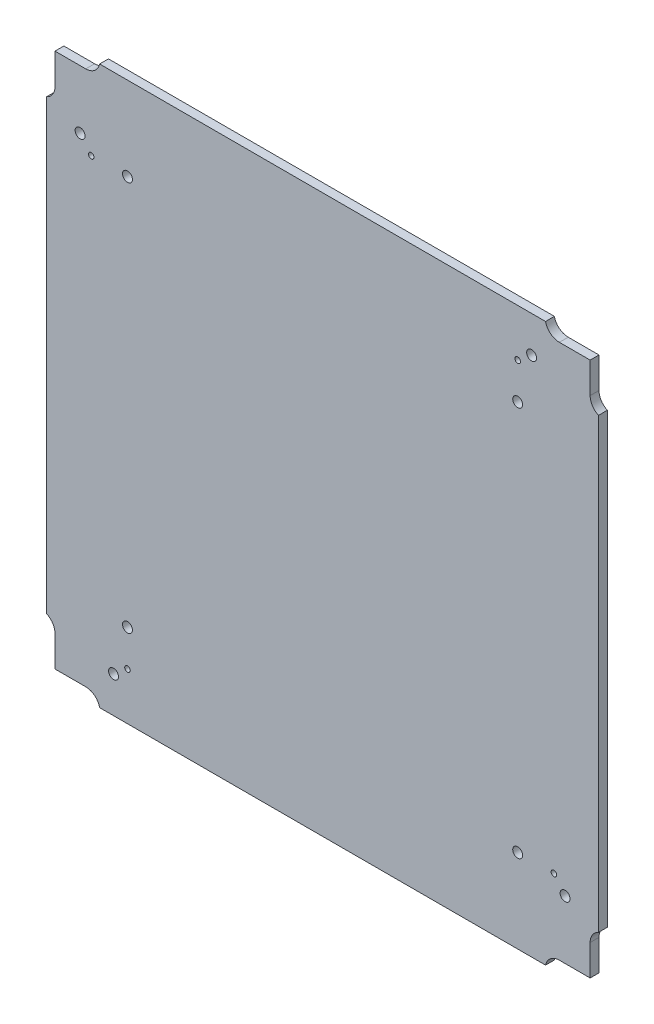
SolidWorks part; units mm, degrees
ref_plane "Front Plane" through (0, 0, 0) normal (0, 0, 1) x (1, 0, 0)
ref_plane "Top Plane" through (0, 0, 0) normal (0, 1, 0) x (1, 0, 0)
ref_plane "Right Plane" through (0, 0, 0) normal (1, 0, 0) x (0, 0, -1)
sketch "Sketch1" plane through (0, 0, 0) normal (0, 0, 1) x (1, 0, 0)
  line L0 (-40, 50) -> (-40, 48)
  line L1 (-50, -50) -> (50, -50)
  line L2 (-50, -50) -> (-50, 50)
  line L3 (-50, 50) -> (50, 50)
  line L4 (50, -50) -> (50, 50)
  line L5 (-50, -50) -> (50, 50) construction
  line L6 (-50, 50) -> (50, -50) construction
  line L7 (-50, 50) -> (-40, 50)
  line L8 (-50, 50) -> (-50, 40)
  line L9 (-40, 48) -> (-48, 48)
  line L10 (-48, 48) -> (-48, 40)
  line L11 (50, 50) -> (40, 50)
  line L12 (50, 50) -> (50, 40)
  line L13 (-48, 40) -> (-50, 40)
  line L14 (50, 40) -> (48, 40)
  line L15 (-50, -50) -> (-37.8649, -50)
  line L16 (-50, -50) -> (-50, -37.8649)
  line L17 (50, 50) -> (50, 40)
  line L18 (50, 50) -> (40, 50)
  line L19 (50, -50) -> (41.5, -50)
  line L20 (50, -50) -> (50, -41.5)
  line L21 (48, 40) -> (48, 48)
  line L22 (48, 48) -> (40, 48)
  line L23 (40, 48) -> (40, 50)
  line L24 (40, -50) -> (40, -48)
  line L25 (50, -50) -> (40, -50)
  line L26 (50, -50) -> (50, -40)
  line L27 (40, -48) -> (48, -48)
  line L28 (48, -48) -> (48, -40)
  line L29 (48, -40) -> (50, -40)
  line L30 (-50, -40) -> (-48, -40)
  line L31 (-50, -50) -> (-50, -40)
  line L32 (-50, -50) -> (-40, -50)
  line L33 (-48, -40) -> (-48, -48)
  line L34 (-48, -48) -> (-40, -48)
  line L35 (-40, -48) -> (-40, -50)
  point P0 (0, 0)
  point P38 (0, 0)
  dimension "D1" = 100
  dimension "D2" = 100
  dimension "D3" = 2
  dimension "D4" = 10
  dimension "D5" = 4
extrude "Boss-Extrude1" add sketch "Sketch1" along normal blind 1.5875 contours L1 L4 L3 L2 region at (0, 0, 0)
fillet "Fillet1" radius 2.54 8 edges at (-48, -40, 0.7937) (-40, -48, 0.7937) (40, -48, 0.7937) (48, -40, 0.7937) (48, 40, 0.7937) (40, 48, 0.7937) (-40, 48, 0.7937) (-48, 40, 0.7937)
sketch "Sketch5" plane through (0, 0, 1.5875) normal (0, 0, 1) x (1, 0, 0)
  line L0 (0, 50) -> (0, -50) construction
  line L5 (-40, 50) -> (40, 50) construction
  line L6 (-40, -50) -> (40, -50) construction
  line L8 (-35.7478, 50) -> (8.2522, 50) construction
  line L9 (-35.7478, 50) -> (-35.7478, 45.8) construction
  line L10 (-35.7478, 45.8) -> (8.2522, 45.8) construction
  line L11 (8.2522, 50) -> (8.2522, 45.8) construction
  circle A0 centre (-35, 43.55) radius 0.395
  circle A1 centre (-33, 43.55) radius 0.395
  circle A2 centre (-31, 43.55) radius 0.395
  circle A3 centre (-29, 43.55) radius 0.395
  circle A4 centre (-27, 43.55) radius 0.395
  circle A5 centre (-25, 43.55) radius 0.395
  circle A6 centre (-23, 43.55) radius 0.395
  circle A7 centre (-21, 43.55) radius 0.395
  circle A8 centre (-19, 43.55) radius 0.395
  circle A9 centre (-17, 43.55) radius 0.395
  circle A10 centre (-15, 43.55) radius 0.395
  circle A11 centre (-13, 43.55) radius 0.395
  circle A12 centre (-11, 43.55) radius 0.395
  circle A13 centre (-9, 43.55) radius 0.395
  circle A14 centre (-7, 43.55) radius 0.395
  circle A15 centre (-5, 43.55) radius 0.395
  circle A16 centre (-3, 43.55) radius 0.395
  circle A17 centre (-1, 43.55) radius 0.395
  circle A18 centre (1, 43.55) radius 0.395
  circle A19 centre (3, 43.55) radius 0.395
  circle A20 centre (5, 43.55) radius 0.395
  circle A21 centre (7, 43.55) radius 0.395
  circle A22 centre (-33, 41.55) radius 0.395
  circle A23 centre (-31, 41.55) radius 0.395
  circle A24 centre (-29, 41.55) radius 0.395
  circle A25 centre (-27, 41.55) radius 0.395
  circle A26 centre (-25, 41.55) radius 0.395
  circle A27 centre (-23, 41.55) radius 0.395
  circle A28 centre (-21, 41.55) radius 0.395
  circle A29 centre (-19, 41.55) radius 0.395
  circle A30 centre (-17, 41.55) radius 0.395
  circle A31 centre (-15, 41.55) radius 0.395
  circle A32 centre (-13, 41.55) radius 0.395
  circle A33 centre (-11, 41.55) radius 0.395
  circle A34 centre (-9, 41.55) radius 0.395
  circle A35 centre (-7, 41.55) radius 0.395
  circle A36 centre (-5, 41.55) radius 0.395
  circle A37 centre (-3, 41.55) radius 0.395
  circle A38 centre (-1, 41.55) radius 0.395
  circle A39 centre (1, 41.55) radius 0.395
  circle A40 centre (3, 41.55) radius 0.395
  circle A41 centre (5, 41.55) radius 0.395
  circle A42 centre (7, 41.55) radius 0.395
  circle A43 centre (-35, 41.55) radius 0.395
  dimension "D5" = 0.79
  dimension "D2" = 2.25
  dimension "D3" = 2
  dimension "D4" = 2
  dimension "D8" = 29
  dimension "D9" = 44
  dimension "D10" = 4.2
  dimension "D6" = 22
  dimension "D7" = 2
sketch "Sketch6" plane through (0, 0, 1.5875) normal (0, 0, 1) x (1, 0, 0)
  line L0 (-40, 50) -> (40, 50) construction
  line L1 (-49.5, 50) -> (49.5, 50)
  line L2 (-49.5, 50) -> (-49.5, -50)
  line L3 (-49.5, -50) -> (49.5, -50)
  line L4 (49.5, 50) -> (49.5, -50)
  line L5 (-40, -50) -> (40, -50) construction
  line L6 (50, -40) -> (50, 40) construction
  dimension "D1" = 99
  dimension "D2" = 0.5
extrude "Cut-Extrude2" cut sketch "Sketch6" against normal through all flip side to cut
sketch "Sketch2" plane through (0, 0, 1.5875) normal (0, 0, 1) x (1, 0, 0)
  line L0 (-36.5, 41) -> (36.5, 41)
  line L1 (-39, 38.5) -> (-36.5, 41)
  line L2 (39, 38.5) -> (39, 26.5)
  line L3 (36.5, 24) -> (-36.5, 24)
  line L4 (-39, 26.5) -> (-39, 38.5)
  line L5 (-36.5, 24) -> (-39, 26.5)
  line L6 (0, 0) -> (0, 50) construction
  line L7 (36.5, 41) -> (39, 38.5)
  line L8 (39, 26.5) -> (36.5, 24)
  line L9 (-36.5, 22.75) -> (36.5, 22.75)
  line L10 (-39, 20.25) -> (-36.5, 22.75)
  line L11 (39, 20.25) -> (39, 8.25)
  line L12 (36.5, 5.75) -> (-36.5, 5.75)
  line L13 (-39, 8.25) -> (-39, 20.25)
  line L14 (-36.5, 5.75) -> (-39, 8.25)
  line L15 (36.5, 22.75) -> (39, 20.25)
  line L16 (39, 8.25) -> (36.5, 5.75)
  line L17 (-36.5, 4.5) -> (36.5, 4.5)
  line L18 (-39, 2) -> (-36.5, 4.5)
  line L19 (39, 2) -> (39, -10)
  line L20 (36.5, -12.5) -> (-36.5, -12.5)
  line L21 (-39, -10) -> (-39, 2)
  line L22 (-36.5, -12.5) -> (-39, -10)
  line L23 (36.5, 4.5) -> (39, 2)
  line L24 (39, -10) -> (36.5, -12.5)
  line L25 (-36.5, -13.75) -> (36.5, -13.75)
  line L26 (-39, -16.25) -> (-36.5, -13.75)
  line L27 (39, -16.25) -> (39, -28.25)
  line L28 (36.5, -30.75) -> (-36.5, -30.75)
  line L29 (-39, -28.25) -> (-39, -16.25)
  line L30 (-40, 50) -> (40, 50) construction
  line L33 (-36.5, -30.75) -> (-39, -28.25)
  line L34 (36.5, -13.75) -> (39, -16.25)
  line L36 (39, -28.25) -> (36.5, -30.75)
  line L37 (-36.5, -32) -> (36.5, -32)
  line L38 (-39, -34.5) -> (-36.5, -32)
  line L39 (39, -34.5) -> (39, -46.5)
  line L40 (36.5, -49) -> (-36.5, -49)
  line L41 (-39, -46.5) -> (-39, -34.5)
  line L42 (-36.5, -49) -> (-39, -46.5)
  line L43 (36.5, -32) -> (39, -34.5)
  line L44 (39, -46.5) -> (36.5, -49)
  line L45 (-40, -50) -> (40, -50) construction
  point P0 (-39, 41)
  point P3 (39, 41)
  point P4 (39, 24)
  point P5 (-39, 24)
  point P19 (-39, 22.75)
  point P21 (39, 22.75)
  point P22 (39, 5.75)
  point P23 (-39, 5.75)
  point P31 (-39, 4.5)
  point P33 (39, 4.5)
  point P34 (39, -12.5)
  point P35 (-39, -12.5)
  point P43 (-39, -13.75)
  point P45 (39, -13.75)
  point P46 (39, -30.75)
  point P47 (-39, -30.75)
  point P55 (-39, -32)
  point P57 (39, -32)
  point P58 (39, -49)
  point P59 (-39, -49)
  dimension "D1" = 78
  dimension "D2" = 17
  dimension "D3" = 5
  dimension "D4" = 1
  dimension "D5" = 9
hole_wizard "Ø1.0 (1) Diameter Hole1" positions "Sketch8" profile "Sketch9" hole size "Ø1.0" standard "ISO" end condition through all
sketch "Sketch8" plane through (0, 0, 1.5875) normal (0, 0, 1) x (1, 0, 0)
  line L0 (-49.5, 40.1646) -> (-49.5, -40.1646) construction
  line L2 (-40, 50) -> (40, 50) construction
  point P0 (-41.5, 35)
  dimension "D1" = 8
  dimension "D2" = 15
sketch "Sketch9" plane through (-41.5, 35, 1.5875) normal (1, 0, 0) x (0, -1, 0)
  line L0 (0, 0) -> (0, 1.5875)
  line L1 (0, 1.5875) -> (0.5, 1.5875)
  line L2 (0.5, 1.5875) -> (0.5, 0)
  line L5 (0.5, 0) -> (0, 0)
  line L11 (0, -6.35) -> (0, 107.95) construction
  dimension "Thru Hole Dia." = 1
  dimension "Thru Hole Depth" = 1.5875
hole_wizard "#0 Clearance Hole1" positions "Sketch11" profile "Sketch10" hole size "#0" standard "ANSI Inch" end condition through all
sketch "Sketch11" plane through (0, 0, 1.5875) normal (0, 0, 1) x (1, 0, 0)
  point P0 (-43.5, 37.5)
  point P4 (-35, 35)
sketch "Sketch10" plane through (-43.5, 37.5, 1.5875) normal (1, 0, 0) x (0, -1, 0)
  line L0 (0, 0) -> (0, 1.5875)
  line L1 (0, 1.5875) -> (0.889, 1.5875)
  line L2 (0.889, 1.5875) -> (0.889, 0)
  line L5 (0.889, 0) -> (0, 0)
  line L11 (0, -6.35) -> (0, 107.95) construction
  dimension "Thru Hole Dia." = 1.778
  dimension "Thru Hole Depth" = 1.5875
ref_axis "Axis1" through (0, 0, 0) along (0, 0, 1)
pattern_circular "CirPattern1" count 4 over 360 about axis through (0, 0, 0) along (0, 0, 1) of "Ø1.0 (1) Diameter Hole1", "#0 Clearance Hole1"
